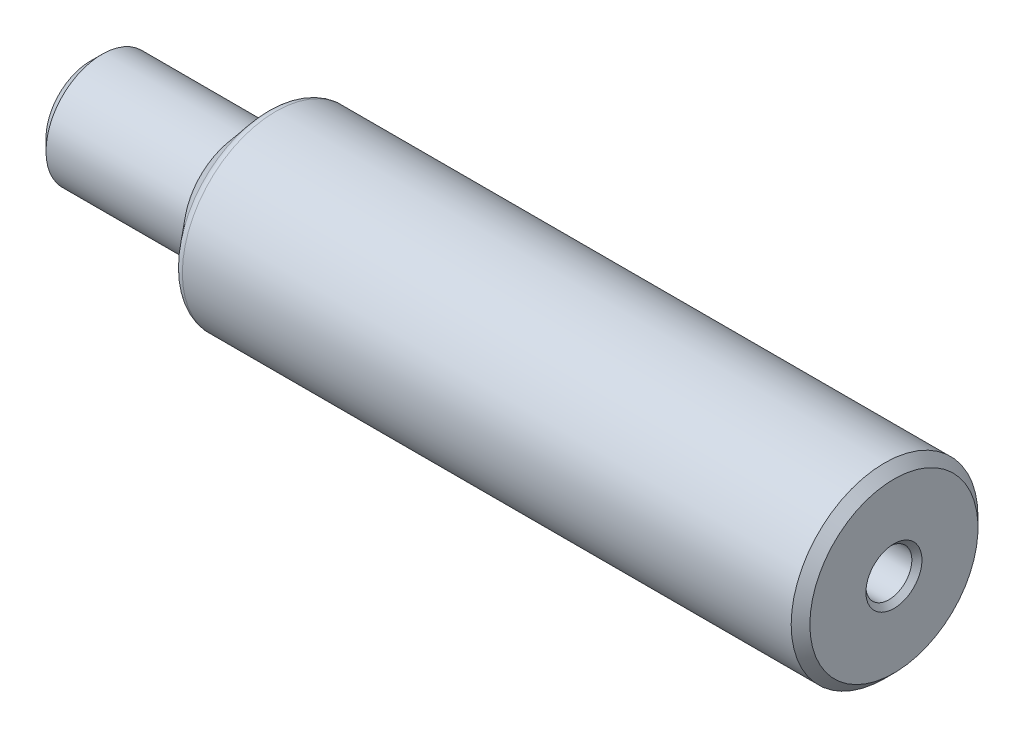
SolidWorks part; units mm, degrees
note: '?' marks a value the reader was unsure of.
material "1023 Carbon Steel Sheet (SS)"
ref_plane "Front Plane" through (0, 0, 0) normal (0, 0, 1) x (1, 0, 0)
ref_plane "Top Plane" through (0, 0, 0) normal (0, 1, 0) x (1, 0, 0)
ref_plane "Right Plane" through (0, 0, 0) normal (1, 0, 0) x (0, 0, -1)
ref_plane "Plane1" through (0, 0, 0) normal (0, 0, 1) x (1, 0, 0)
sketch "Sketch1" plane through (0, 0, 0) normal (0, 0, 1) x (1, 0, 0)
  line L0 (0, 0) -> (0, 4.5)
  line L1 (0, 4.5) -> (0.5, 5)
  line L2 (0.5, 5) -> (34.5, 5)
  line L3 (34.5, 5) -> (35, 4.5)
  line L4 (35, 4.5) -> (35, 0)
  line L5 (35, 0) -> (0, 0)
  line L6 (35, 0) -> (0, 0) construction
revolve "Revolve1" add sketch "Sketch1" angle 360 about L6
ref_plane "Plane2" through (0, 0, 0) normal (0, 0, 1) x (1, 0, 0)
sketch "Sketch2" plane through (0, 0, 0) normal (0, 0, 1) x (1, 0, 0)
  line L0 (-8, 0) -> (-8, 2.3865)
  line L1 (-8, 2.3865) -> (-7.3865, 3)
  line L2 (-7.3865, 3) -> (0, 3)
  line L3 (0, 3) -> (0, 0)
  line L4 (0, 0) -> (-8, 0)
  line L5 (0, 0) -> (-8, 0) construction
revolve "Revolve2" add sketch "Sketch2" angle 360 about L5
cosmetic thread "Cosmetic Thread1" parameters "D1"=6, "D2"=4.773
ref_plane "Plane3" through (0, 0, 0) normal (0, 0, 1) x (1, 0, 0)
sketch "Sketch3" plane through (0, 0, 0) normal (0, 0, 1) x (1, 0, 0)
  line L0 (20.5, 0) -> (21.2099, 1.2295)
  line L1 (21.2099, 1.2295) -> (34.7295, 1.2295)
  line L2 (34.7295, 1.2295) -> (35, 1.5)
  line L3 (35, 1.5) -> (35, 0)
  line L4 (35, 0) -> (20.5, 0)
  line L5 (35, 0) -> (20.5, 0) construction
revolve "Cut-Revolve1" cut sketch "Sketch3" angle 360 about L5
cosmetic thread "Cosmetic Thread2" parameters "D1"=9, "D2"=3
sketch "Sketch5" plane through (0, 0, 0) normal (0, 1, 0) x (1, 0, 0)
  line L0 (0, 3) -> (1.6782, 5)
  line L1 (34.5, 5) -> (0.5, 5) construction
  line L2 (1.6782, 5) -> (0, 5)
  line L3 (0, 5) -> (0, 3)
  dimension "D1" = 40
revolve "Cut-Revolve2" cut sketch "Sketch5" angle 360 about L1
fillet "Fillet1" radius 0.5 1 edges at (1.6782, 0, 5)
ref_axis "Axis1" through (39.3545, 0, 0) along (-1, 0, 0)?
